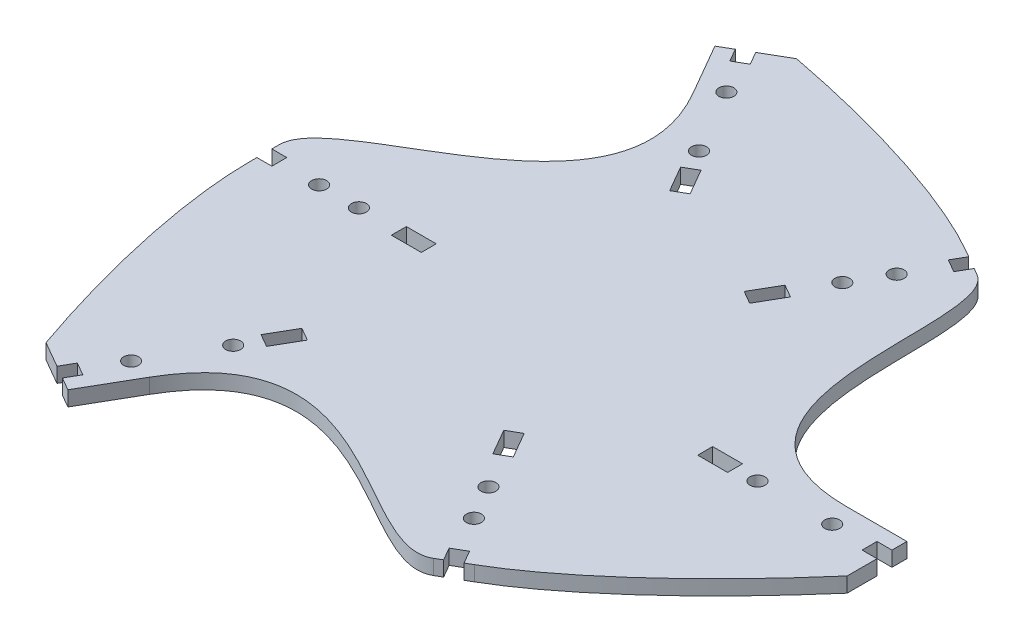
SolidWorks part; units mm, degrees
ref_plane "Front Plane" through (0, 0, 0) normal (0, 0, 1) x (1, 0, 0)
ref_plane "Top Plane" through (0, 0, 0) normal (0, 1, 0) x (1, 0, 0)
ref_plane "Right Plane" through (0, 0, 0) normal (1, 0, 0) x (0, 0, -1)
sketch "Sketch1" plane through (0, 0, 0) normal (0, 1, 0) x (1, 0, 0)
  line L0 (76.2, 0) -> (0, 0) construction
  line L1 (38.1, 65.9911) -> (0, 0) construction
  line L2 (-40.8496, -64.4036) -> (-43.5993, -62.8161)
  line L3 (76.2, -3.175) -> (76.2, -6.35)
  line L4 (15.6623, 23.9529) -> (18.8373, 29.4522)
  line L5 (15.6623, 23.9529) -> (12.9127, 25.5404)
  line L6 (-76.2, -989.805) -> (-76.2, 49010.195) construction
  line L7 (29.0004, 56.5801) -> (34.4996, 53.4051) construction
  line L8 (18.8373, 29.4522) -> (16.0877, 31.0397)
  line L9 (12.9127, 25.5404) -> (16.0877, 31.0397)
  line L10 (76.2, -3.175) -> (63.5, -3.175)
  line L11 (11.6658, 66.5882) -> (40.903, 49.7081) construction
  line L12 (38.3255, -3.175) -> (89.1889, -3.175) construction
  line L14 (15.6623, 23.9529) -> (16.0877, 31.0397) construction
  line L15 (18.8373, 29.4522) -> (12.9127, 25.5404) construction
  line L16 (76.2, -6.35) -> (73.025, -6.35)
  line L17 (38.1, -6.35) -> (44.45, -6.35)
  line L18 (38.1, -6.35) -> (38.1, -9.525)
  line L19 (38.1, -9.525) -> (44.45, -9.525)
  line L20 (44.45, -6.35) -> (44.45, -9.525)
  line L21 (38.1, -6.35) -> (44.45, -9.525) construction
  line L22 (38.1, -9.525) -> (44.45, -6.35) construction
  line L23 (73.025, -6.35) -> (73.025, -9.525)
  line L24 (73.025, -9.525) -> (76.2, -9.525)
  line L25 (38.1, -7.9375) -> (73.025, -7.9375) construction
  line L26 (76.2, -9.525) -> (76.2, -15.875)
  line L27 (30.3752, 55.7864) -> (28.7877, 53.0367)
  line L28 (28.7877, 53.0367) -> (31.5373, 51.4492)
  line L29 (31.5373, 51.4492) -> (33.1248, 54.1989)
  line L30 (29.0004, 56.5801) -> (30.3752, 55.7864)
  line L31 (33.1248, 54.1989) -> (34.4996, 53.4051)
  line L32 (76.2, -3.175) -> (76.2, -15.875) construction
  line L33 (12.9127, -25.5404) -> (16.0877, -31.0397)
  line L34 (12.9127, -25.5404) -> (15.6623, -23.9529)
  line L35 (16.0877, -31.0397) -> (18.8373, -29.4522)
  line L36 (15.6623, -23.9529) -> (18.8373, -29.4522)
  line L37 (-40.8496, -64.4036) -> (-34.4996, -53.4051)
  line L38 (-43.5993, -62.8161) -> (-42.0118, -60.0665)
  line L39 (-24.5493, -29.8206) -> (-27.7243, -35.3198)
  line L40 (-24.5493, -29.8206) -> (-27.2989, -28.2331)
  line L41 (-27.2989, -28.2331) -> (-30.4739, -33.7323)
  line L42 (-27.7243, -35.3198) -> (-30.4739, -33.7323)
  line L43 (-42.0118, -60.0665) -> (-44.7614, -58.479)
  line L44 (-44.7614, -58.479) -> (-46.3489, -61.2286)
  line L45 (-46.3489, -61.2286) -> (-51.8482, -58.0536)
  line L46 (33.1248, -54.1989) -> (31.5373, -51.4492)
  line L47 (31.5373, -51.4492) -> (28.7877, -53.0367)
  line L48 (28.7877, -53.0367) -> (30.3752, -55.7864)
  line L49 (34.4996, -53.4051) -> (33.1248, -54.1989)
  line L50 (30.3752, -55.7864) -> (29.0004, -56.5801)
  line L51 (-38.1, -65.9911) -> (0, 0) construction
  line L52 (38.1, -65.9911) -> (0, 0) construction
  line L53 (34.4996, -53.4051) -> (29.0004, -56.5801) construction
  line L54 (12.9127, -25.5404) -> (18.8373, -29.4522) construction
  line L55 (16.0877, -31.0397) -> (15.6623, -23.9529) construction
  line L56 (-24.5493, -29.8206) -> (-30.4739, -33.7323) construction
  line L57 (-27.2989, -28.2331) -> (-27.7243, -35.3198) construction
  line L58 (-25.9241, -29.0268) -> (-43.3866, -59.2728) construction
  line L59 (-40.8496, -64.4036) -> (-51.8482, -58.0536) construction
  line L60 (-35.3504, 67.5786) -> (-32.6007, 69.1661)
  line L61 (-28.575, 1.5875) -> (-34.925, 1.5875)
  line L62 (-28.575, 1.5875) -> (-28.575, -1.5875)
  line L63 (-34.925, 1.5875) -> (-34.925, -1.5875)
  line L64 (-28.575, -1.5875) -> (-34.925, -1.5875)
  line L65 (-35.3504, 67.5786) -> (-29.0004, 56.5801)
  line L66 (-32.6007, 69.1661) -> (-31.0132, 66.4165)
  line L67 (-13.5507, 36.1706) -> (-16.7257, 41.6698)
  line L68 (-13.5507, 36.1706) -> (-10.8011, 37.7581)
  line L69 (-10.8011, 37.7581) -> (-13.9761, 43.2573)
  line L70 (-16.7257, 41.6698) -> (-13.9761, 43.2573)
  line L71 (-31.0132, 66.4165) -> (-28.2636, 68.004)
  line L72 (-28.2636, 68.004) -> (-29.8511, 70.7536)
  line L73 (-29.8511, 70.7536) -> (-24.3518, 73.9286)
  line L74 (-63.5, -1.5875) -> (-60.325, -1.5875)
  line L75 (-60.325, -1.5875) -> (-60.325, 1.5875)
  line L76 (-60.325, 1.5875) -> (-63.5, 1.5875)
  line L77 (-63.5, -3.175) -> (-63.5, -1.5875)
  line L78 (-63.5, 1.5875) -> (-63.5, 3.175)
  line L79 (-38.1, 65.9911) -> (0, 0) construction
  line L80 (-76.2, 0) -> (0, 0) construction
  line L81 (-63.5, -3.175) -> (-63.5, 3.175) construction
  line L82 (-28.575, 1.5875) -> (-34.925, -1.5875) construction
  line L83 (-34.925, 1.5875) -> (-28.575, -1.5875) construction
  line L84 (-13.5507, 36.1706) -> (-13.9761, 43.2573) construction
  line L85 (-10.8011, 37.7581) -> (-16.7257, 41.6698) construction
  line L86 (-12.1759, 36.9643) -> (-29.6384, 67.2103) construction
  line L87 (-35.3504, 67.5786) -> (-24.3518, 73.9286) construction
  circle A0 centre (0, 0) radius 76.2 construction
  circle A1 centre (65.0875, -7.9375) radius 1.5875
  circle A2 centre (49.2125, -7.9375) radius 1.5875
  circle A3 centre (25.9334, 44.918) radius 1.5875
  circle A4 centre (21.7043, 37.593) radius 1.5875
  circle A5 centre (-39.4178, -52.3987) radius 1.5875
  circle A6 centre (-31.4803, -38.6505) radius 1.5875
  circle A7 centre (25.9334, -44.918) radius 1.5875
  circle A8 centre (21.7043, -37.593) radius 1.5875
  circle A9 centre (-25.6697, 60.3362) radius 1.5875
  circle A10 centre (-17.7322, 46.588) radius 1.5875
  circle A11 centre (-51.8668, 0) radius 1.5875
  circle A12 centre (-43.4086, 0) radius 1.5875
  spline S0 degree 3 poles (63.5, -3.175) (26.0624, -3.175) (45.6203, 46.9846) (34.4996, 53.4051) knots 0 0 0 0 1 1 1 1
  spline S1 degree 3 poles (29.0004, 56.5801) (18.1181, 62.863) (-0.9944, 69.4521) (-24.3518, 73.9286) knots 0 0 0 0 1 1 1 1
  spline S2 degree 3 poles (-34.4996, -53.4051) (-15.7808, -20.9832) (17.8797, -63.0006) (29.0004, -56.5801) knots 0 0 0 0 1 1 1 1
  spline S3 degree 3 poles (34.4996, -53.4051) (45.3819, -47.1222) (60.6445, -33.8649) (76.2, -15.875) knots 0 0 0 0 1 1 1 1
  spline S4 degree 3 poles (-29.0004, 56.5801) (-10.2816, 24.1582) (-63.5, 16.016) (-63.5, 3.175) knots 0 0 0 0 1 1 1 1
  spline S5 degree 3 poles (-63.5, -3.175) (-63.5, -15.7408) (-59.6501, -35.5872) (-51.8482, -58.0536) knots 0 0 0 0 1 1 1 1
  point P12 (15.875, 27.4963)
  point P19 (31.75, 54.9926)
  point P31 (41.275, -7.9375)
  point P48 (30.1625, 52.243)
  point P60 (15.875, -27.4963)
  point P70 (-27.5116, -31.7764)
  point P98 (-31.75, 0)
  point P108 (-13.7634, 39.7139)
  dimension "D1" = 152.4
  dimension "D4" = 12.7
  dimension "D5" = 3.175
  dimension "D11" = 3.175
  dimension "D19" = 3.175
  dimension "D22" = 3.175
  dimension "D2" = 60
  dimension "D3" = 3
  dimension "D6" = 3.175
  dimension "D7" = 6.35
  dimension "D8" = 63.5
  dimension "D9" = 6.35
  dimension "D10" = 12.7
  dimension "D12" = 3.175
  dimension "D13" = 28.575
  dimension "D14" = 6.35
  dimension "D15" = 3.175
  dimension "D16" = 3.175
  dimension "D17" = 4.7625
  dimension "D18" = 20.6375
  dimension "D20" = 3.175
  dimension "D21" = 25.4
  dimension "D23" = 8.4582
  dimension "D24" = 8.4582
extrude "Boss-Extrude1" add sketch "Sketch1" along normal blind 3.175
